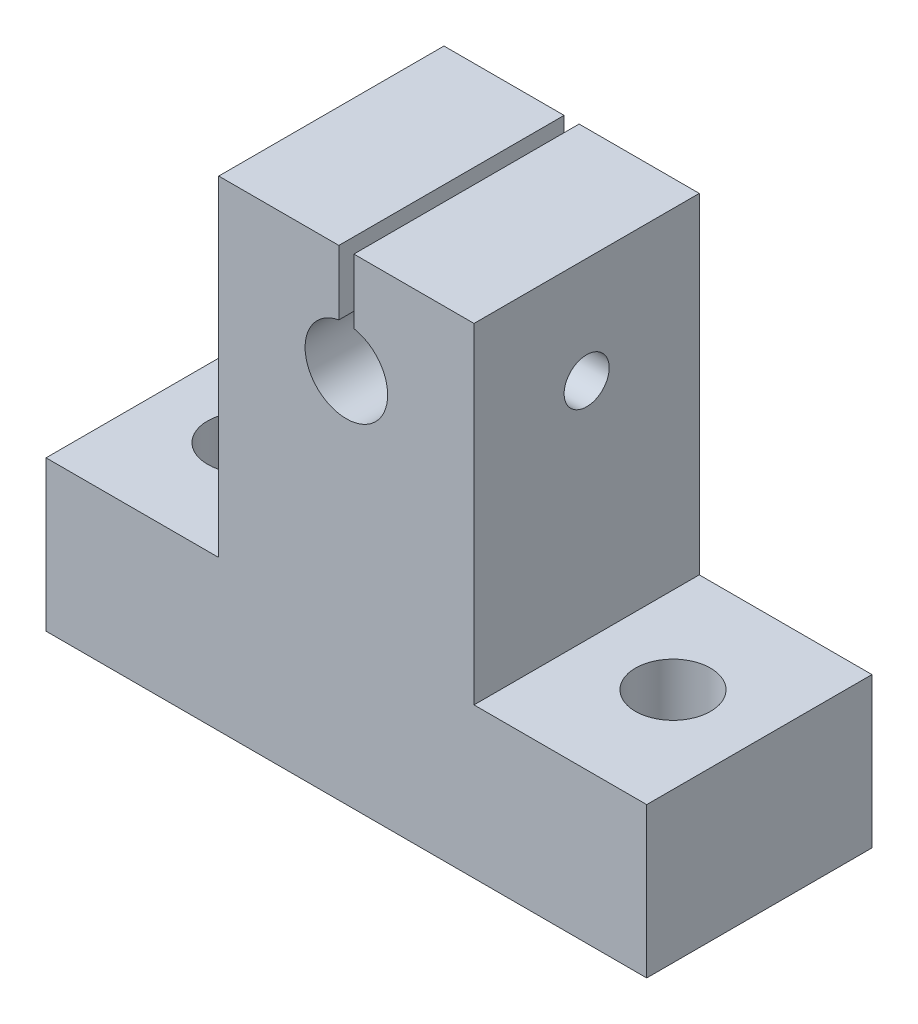
SolidWorks part; units mm, degrees
note: The reader was unsure of these and kept them because the rebuilt part matched: shared geometry of "Croquis1<3>".
ref_plane "Front Plane" through (0, 0, 0) normal (0, 0, 1) x (1, 0, 0)
ref_plane "Top Plane" through (0, 0, 0) normal (0, 1, 0) x (1, 0, 0)
ref_plane "Right Plane" through (0, 0, 0) normal (1, 0, 0) x (0, 0, -1)
sketch "Croquis1" plane through (0, 0, 0) normal (0, 1, 0) x (1, 0, 0)
  line L1 (-20, 7.5) -> (20, 7.5)
  line L2 (-20, 7.5) -> (-20, -7.5)
  line L3 (-20, -7.5) -> (20, -7.5)
  line L4 (20, 7.5) -> (20, -7.5)
  line L5 (-20, 7.5) -> (20, -7.5) construction
  line L6 (-20, -7.5) -> (20, 7.5) construction
  line L7 (-8.5, -7.5) -> (8.5, -7.5)
  line L8 (-8.5, -7.5) -> (-8.5, 7.5)
  line L9 (-8.5, 7.5) -> (8.5, 7.5)
  line L10 (8.5, -7.5) -> (8.5, 7.5)
  line L11 (-8.5, -7.5) -> (8.5, 7.5) construction
  line L12 (-8.5, 7.5) -> (8.5, -7.5) construction
  point P0 (0, 0)
  point P7 (0, 0)
  dimension "D1" = 40
  dimension "D2" = 15
  dimension "D3" = 17
  dimension "D4" = 15
extrude "Saliente-Extruir1" add sketch "Croquis1" along normal blind 32 contours L3 L10 L1 L8
extrude "Saliente-Extruir2" add sketch "Croquis1<3>" along normal blind 10 contours L3 L8 L1 L2 | L10 L3 L4 L1
sketch "Croquis1<3>" plane through (0, 0, 0) normal (0, 1, 0) x (1, 0, 0) same geometry as "Croquis1"
sketch "Croquis2" plane through (0, 0, -7.5) normal (0, 0, -1) x (-1, 0, 0)
  line L0 (20, 0) -> (-20, 0) construction
  line L1 (-0.5, 32) -> (-0.5, 27.7042)
  line L2 (8.5, 32) -> (-8.5, 32) construction
  line L3 (0, 32) -> (0, 31.0218) construction
  line L4 (0.5, 32) -> (0.5, 27.7042)
  circle A0 centre (0, 25) radius 2.75
  dimension "D1" = 5.5
  dimension "D2" = 25
  dimension "D3" = 0.5
extrude "Cortar-Extruir1" cut sketch "Croquis2" against normal blind 20
sketch "Croquis3" plane through (0, 10, 0) normal (0, 1, 0) x (1, 0, 0)
  line L0 (8.5, -7.5) -> (20, -7.5) construction
  line L1 (0, 0) -> (0, -4.979) construction
  circle A0 centre (14.25, 0) radius 2.5
  circle A1 centre (-14.25, 0) radius 2.5
  point P5 (14.25, -7.5)
  dimension "D1" = 5
extrude "Cortar-Extruir2" cut sketch "Croquis3" against normal blind 20
sketch "Croquis4" plane through (-8.5, 0, 0) normal (-1, 0, 0) x (0, 0, 1)
  circle A0 centre (0, 24.9436) radius 1.5
  dimension "D1" = 3
extrude "Cortar-Extruir3" cut sketch "Croquis4" against normal blind 20
